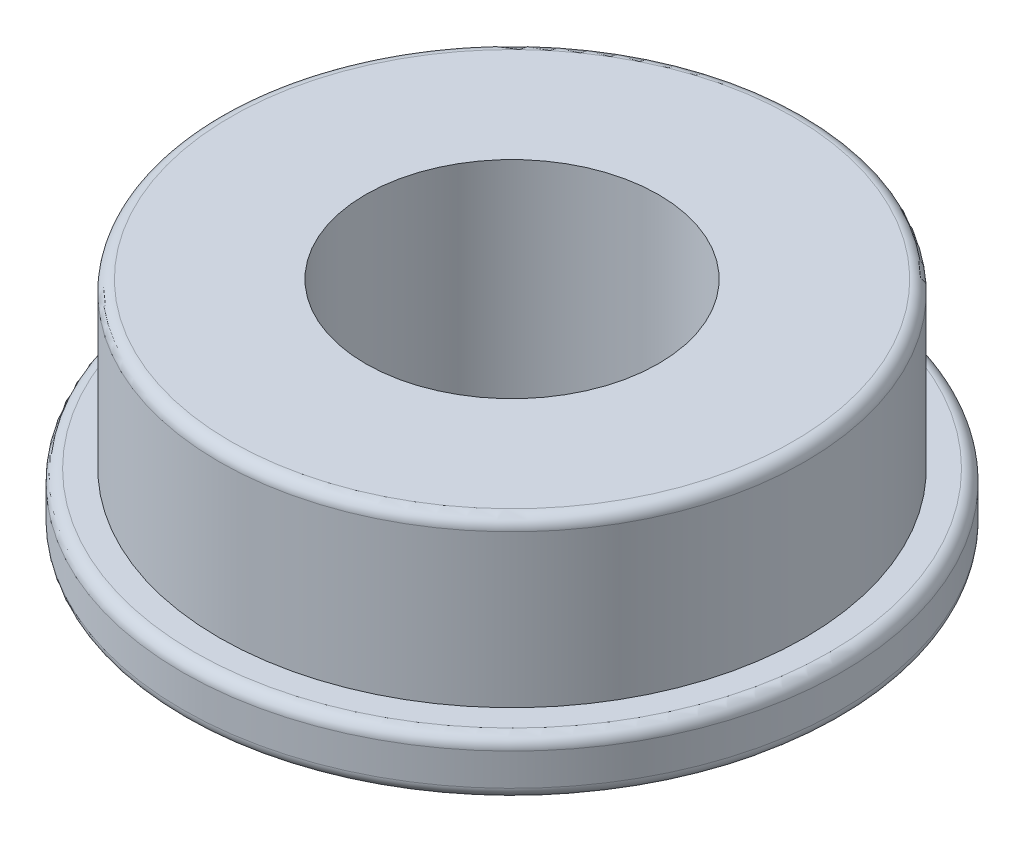
SolidWorks part; units mm, degrees
ref_plane "Front Plane" through (0, 0, 0) normal (0, 0, 1) x (1, 0, 0)
ref_plane "Top Plane" through (0, 0, 0) normal (0, 1, 0) x (1, 0, 0)
ref_plane "Right Plane" through (0, 0, 0) normal (1, 0, 0) x (0, 0, -1)
sketch "Sketch1" plane through (0, 0, 0) normal (0, 1, 0) x (1, 0, 0)
  circle A0 centre (0, 0) radius 3.175
  circle A1 centre (0, 0) radius 6.35
  circle A2 centre (0, 0) radius 7.1438
  dimension "D1" = 6.35
  dimension "D2" = 12.7
  dimension "D3" = 0.7937
extrude "Boss-Extrude1" add sketch "Sketch1" along normal blind 4.7625 contours A1 A0 region at (-6.1704, 0, 0)
extrude "Boss-Extrude2" add sketch "Sketch1<3>" along normal blind 1.2065 contours A2 A1 region at (-6.9417, 0, 0)
sketch "Sketch1<3>" plane through (0, 0, 0) normal (0, 1, 0) x (1, 0, 0) same geometry as "Sketch1"
fillet "Fillet1" radius 0.254 3 edges at (0, 0, 7.1438) (0, 1.2065, 7.1438) (0, 4.7625, 6.35)
